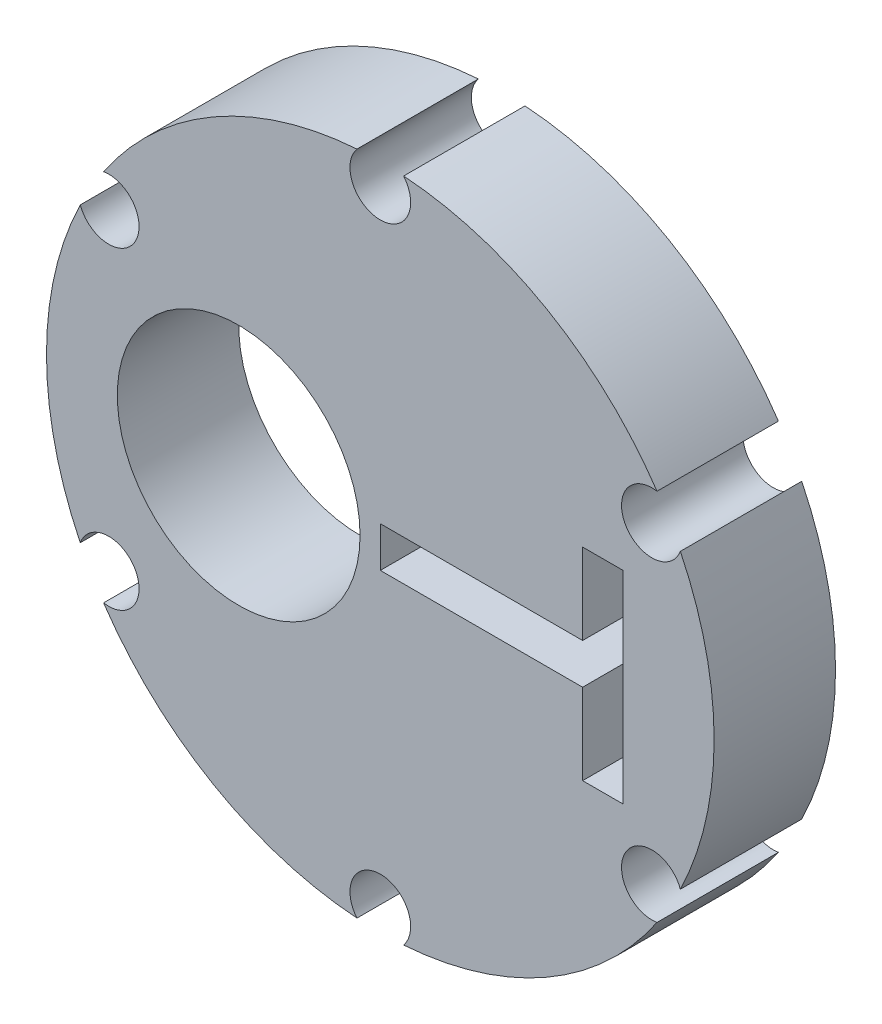
SolidWorks part; units mm, degrees
material "ABS"
ref_plane "Front Plane" through (0, 0, 0) normal (0, 0, 1) x (1, 0, 0)
ref_plane "Top Plane" through (0, 0, 0) normal (0, 1, 0) x (1, 0, 0)
ref_plane "Right Plane" through (0, 0, 0) normal (1, 0, 0) x (0, 0, -1)
sketch "Sketch1" plane through (0, 0, 0) normal (0, 0, 1) x (1, 0, 0)
  circle A0 centre (0, 0) radius 16.5
  dimension "D1" = 33
extrude "Boss-Extrude1" add sketch "Sketch1" along normal blind 6
sketch "Sketch2" plane through (0, 0, 6) normal (0, 0, 1) x (1, 0, 0)
  circle A0 centre (0, 15.5) radius 1.5
  circle A1 centre (13.4234, 7.75) radius 1.5
  circle A2 centre (13.4234, -7.75) radius 1.5
  circle A3 centre (0, -15.5) radius 1.5
  circle A4 centre (-13.4234, -7.75) radius 1.5
  circle A5 centre (-13.4234, 7.75) radius 1.5
  point P15 (0, 0)
  dimension "D1" = 3
  dimension "D2" = 15.5
  dimension "D3" = 6
extrude "Cut-Extrude1" cut sketch "Sketch2" against normal through all
sketch "Sketch3" plane through (0, 0, 6) normal (0, 0, 1) x (1, 0, 0)
  line L0 (-7, 0) -> (0, 0) construction
  circle A0 centre (-7, 0) radius 6
  dimension "D1" = 12
  dimension "D3" = 7
extrude "Cut-Extrude2" cut sketch "Sketch3" against normal through all
sketch "Sketch5" plane through (0, 0, 6) normal (0, 0, 1) x (1, 0, 0)
  line L1 (12, 5) -> (10, 5)
  line L2 (12, 5) -> (12, -5)
  line L3 (12, -5) -> (10, -5)
  line L4 (10, 5) -> (10, 1)
  line L5 (10, -1) -> (10, -5)
  line L6 (0, 1) -> (10, 1)
  line L7 (0, 1) -> (0, -1)
  line L8 (0, -1) -> (10, -1)
  point P10 (0, 0)
  dimension "D1" = 10
  dimension "D2" = 2
extrude "Cut-Extrude3" cut sketch "Sketch5" against normal through all
equation "\"smallPulleyTeeth\"= 15"
equation "\"largePulleyTeeth\"= 30"
equation "\"eighthThick\"= 2.9mm"
equation "\"sixteenthThick\" = 1.7mm"
equation "\"wheelEighthThick\"=3.0mm"
equation "\"quarterThick\"=6.0mm"
equation "\"OD\" = 146mm"
equation "\"puckAngle\" = 60.5deg"
equation "\"puckDiam\" = 76.5mm"
equation "\"axlePress\" = 5.9mm"
equation "\"D1@Boss-Extrude1\"=\"quarterThick\""
